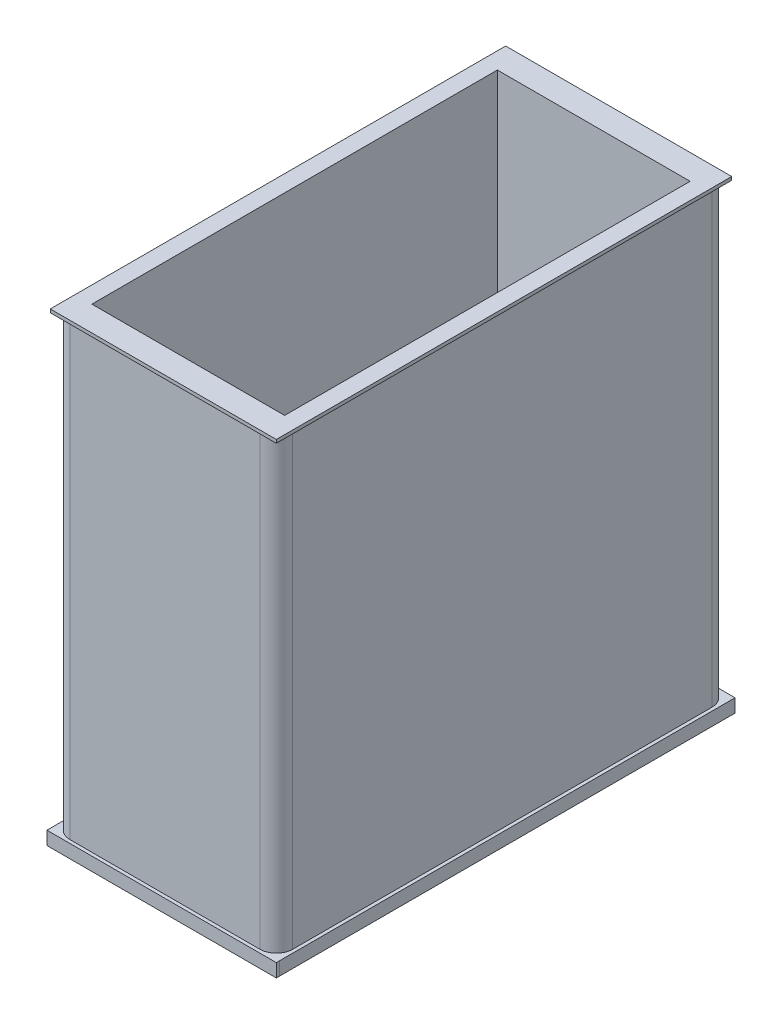
SolidWorks part; units mm, degrees
other "Camera1"
ref_plane "Front Plane" through (0, 0, 0) normal (0, 0, 1) x (1, 0, 0)
ref_plane "Top Plane" through (0, 0, 0) normal (0, 1, 0) x (1, 0, 0)
ref_plane "Right Plane" through (0, 0, 0) normal (1, 0, 0) x (0, 0, -1)
sketch "Sketch1" plane through (0, 0, 0) normal (0, 1, 0) x (1, 0, 0)
  line L2 (-66.3338, 134.988) -> (103.5922, 134.988)
  line L3 (-66.3338, 134.988) -> (-66.3338, -209.944)
  line L4 (-66.3338, -209.944) -> (103.5922, -209.944)
  line L5 (103.5922, 134.988) -> (103.5922, -209.944)
  dimension "D1" = 344.932
  dimension "D2" = 169.926
extrude "Boss-Extrude1" add sketch "Sketch1" along normal blind 379.984
sketch "Sketch7" plane through (-66.3338, 0, 0) normal (-1, 0, 0) x (0, 0, 1)
  line L0 (-134.988, 0) -> (209.944, 0)
  line L1 (-134.988, 0) -> (-134.988, 10.16)
  line L2 (209.944, 0) -> (209.944, 10.16)
  line L3 (-134.988, 10.16) -> (209.944, 10.16)
  dimension "D1" = 10.16
extrude "Boss-Extrude4" add sketch "Sketch7" along normal blind 2.54
sketch "Sketch8" plane through (103.5922, 0, 0) normal (1, 0, 0) x (0, 0, -1)
  line L0 (-209.944, 0) -> (134.988, 0)
  line L1 (-209.944, 0) -> (-209.944, 10.16)
  line L2 (134.988, 0) -> (134.988, 10.16)
  line L3 (-209.944, 10.16) -> (134.988, 10.16)
  dimension "D1" = 10.16
extrude "Boss-Extrude5" add sketch "Sketch8" along normal blind 2.54
sketch "Sketch9" plane through (0, 0, -134.988) normal (0, 0, -1) x (-1, 0, 0)
  line L0 (-106.1322, 0) -> (68.8738, 0)
  line L1 (-106.1322, 0) -> (-106.1322, 10.16)
  line L2 (68.8738, 0) -> (68.8738, 10.16)
  line L3 (-106.1322, 10.16) -> (68.8738, 10.16)
extrude "Boss-Extrude6" add sketch "Sketch9" along normal blind 2.54
sketch "Sketch13" plane through (103.5922, 0, 0) normal (1, 0, 0) x (0, 0, -1)
  line L0 (-209.944, 354.584) -> (134.988, 354.584)
  line L1 (-209.944, 354.584) -> (-209.944, 352.044)
  line L2 (134.988, 354.584) -> (134.988, 352.044)
  line L3 (-209.944, 352.044) -> (134.988, 352.044)
  line L4 (-209.944, 379.984) -> (-209.944, 10.16) construction
  line L5 (134.988, 379.984) -> (134.988, 10.16) construction
  line L6 (-209.944, 379.984) -> (134.988, 379.984) construction
  dimension "D1" = 2.54
  dimension "D2" = 25.4
extrude "Boss-Extrude9" add sketch "Sketch13" along normal blind 1.27
sketch "Sketch14" plane through (0, 0, -134.988) normal (0, 0, -1) x (-1, 0, 0)
  line L6 (-104.8622, 352.044) -> (66.3338, 352.044)
  line L7 (-104.8622, 352.044) -> (-104.8622, 354.584)
  line L8 (66.3338, 352.044) -> (66.3338, 354.584)
  line L9 (-104.8622, 354.584) -> (66.3338, 354.584)
  line L10 (66.3338, 379.984) -> (66.3338, 10.16) construction
  dimension "D1" = 2.54
extrude "Boss-Extrude10" add sketch "Sketch14" along normal blind 1.27
sketch "Sketch15" plane through (-66.3338, 0, 0) normal (-1, 0, 0) x (0, 0, 1)
  line L0 (-136.258, 352.044) -> (209.944, 352.044)
  line L1 (-136.258, 352.044) -> (-136.258, 354.584)
  line L2 (209.944, 352.044) -> (209.944, 354.584)
  line L3 (-136.258, 354.584) -> (209.944, 354.584)
  line L4 (209.944, 379.984) -> (209.944, 10.16) construction
  dimension "D1" = 2.54
extrude "Boss-Extrude11" add sketch "Sketch15" along normal blind 1.27
sketch "Sketch16" plane through (0, 0, 209.944) normal (0, 0, 1) x (1, 0, 0)
  line L0 (-67.6038, 352.044) -> (104.8622, 352.044)
  line L1 (-67.6038, 352.044) -> (-67.6038, 354.584)
  line L2 (104.8622, 352.044) -> (104.8622, 354.584)
  line L3 (-67.6038, 354.584) -> (104.8622, 354.584)
  dimension "D1" = 2.54
extrude "Boss-Extrude12" add sketch "Sketch16" along normal blind 1.27
ref_plane "Plane3" through (0, 0, -134.988) normal (0, 0, -1) x (-1, 0, 0)
fillet "Fillet1" radius 12.54 10 edges at (18.6292, 379.984, -134.988) (103.5922, 379.984, 37.478) (18.6292, 379.984, 209.944) (-66.3338, 379.984, 37.478) (103.5922, 367.284, -134.988) (-66.3338, 181.102, -134.988) (-66.3338, 181.102, 209.944) (103.5922, 367.284, 209.944) (103.5922, 181.102, -134.988) (103.5922, 181.102, 209.944)
sketch "Sketch23" plane through (0, 0, 209.944) normal (0, 0, 1) x (1, 0, 0)
  line L0 (-68.8738, 10.16) -> (-68.8738, 0)
  line L1 (-68.8738, 10.16) -> (106.141, 10.16)
  line L2 (-68.8738, 0) -> (106.141, 0)
  line L3 (106.141, 10.16) -> (106.141, 0)
extrude "Boss-Extrude15" add sketch "Sketch23" along normal blind 2.54
sketch "Sketch25" plane through (0, 0, -134.988) normal (0, 0, -1) x (-1, 0, 0)
  line L1 (-103.5922, 354.584) -> (76.696, 354.584)
  line L2 (-103.5922, 354.584) -> (-103.5922, 383.24)
  line L3 (-103.5922, 383.24) -> (76.696, 383.24)
  line L4 (76.696, 354.584) -> (76.696, 383.24)
  point P5 (76.696, 383.24)
extrude "Cut-Extrude1" cut sketch "Sketch25" against normal blind 474.472
sketch "Sketch26" plane through (0, 354.584, 0) normal (0, 1, 0) x (1, 0, 0)
  line L0 (104.8622, -211.214) -> (-67.6038, -211.214) construction
  line L1 (-54.9038, 117.208) -> (92.1622, 117.208)
  line L2 (-54.9038, 117.208) -> (-54.9038, -192.164)
  line L3 (-54.9038, -192.164) -> (92.1622, -192.164)
  line L4 (92.1622, 117.208) -> (92.1622, -192.164)
  line L5 (-67.6038, 136.258) -> (104.8622, 136.258) construction
  line L6 (104.8622, 136.258) -> (104.8622, -211.214) construction
  line L7 (-67.6038, -211.214) -> (-67.6038, 136.258) construction
  dimension "D1" = 19.05
  dimension "D2" = 19.05
  dimension "D3" = 12.7
  dimension "D4" = 12.7
extrude "Cut-Extrude2" cut sketch "Sketch26" against normal blind 345.948
